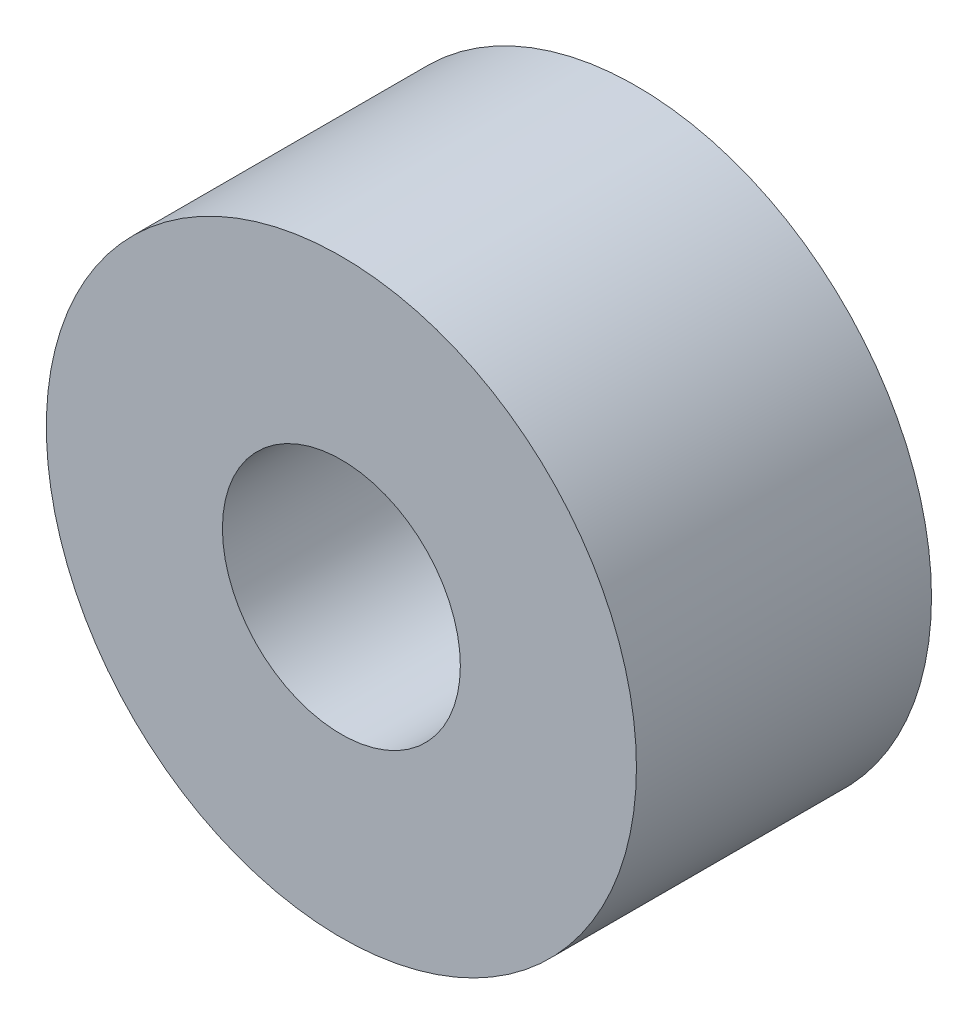
SolidWorks part; units mm, degrees
ref_plane "Front Plane" through (0, 0, 0) normal (0, 0, 1) x (1, 0, 0)
ref_plane "Top Plane" through (0, 0, 0) normal (0, 1, 0) x (1, 0, 0)
ref_plane "Right Plane" through (0, 0, 0) normal (1, 0, 0) x (0, 0, -1)
sketch "Sketch1" plane through (0, 0, 0) normal (1, 0, 0) x (0, 0, -1)
  line L0 (-3.9688, -3.2004) -> (-3.9688, 3.2004) construction
  line L1 (3.9688, -7.9375) -> (-3.9688, -7.9375) construction
  line L2 (3.9688, -7.9375) -> (3.9688, 7.9375) construction
  line L3 (3.9688, 7.9375) -> (-3.9688, 7.9375) construction
  line L4 (-3.9688, -7.9375) -> (-3.9688, 7.9375) construction
  line L5 (0, 7.9375) -> (0, -7.9375) construction
  line L6 (3.9688, 0) -> (-3.9688, 0) construction
  point P0 (0, 0)
  point P7 (-3.9688, 0)
  dimension "D1" = 6.4008
  dimension "D2" = 15.875
sketch "Sketch3" plane through (0, 0, 0) normal (0, 0, 1) x (1, 0, 0)
  circle A0 centre (0, 0) radius 3.2004 construction
  circle A1 centre (0, 0) radius 7.9375 construction
  point P6 (0, -3.2004)
  dimension "OD" = 15.875
  dimension "ID" = 6.4008
sketch "Sketch2" plane through (0, 0, 0) normal (0, 0, 1) x (1, 0, 0)
  circle A0 centre (0, 0) radius 7.9375
  circle A1 centre (0, 0) radius 3.2004
extrude "Extrude1" add sketch "Sketch2" along normal up to vertex and the other way up to vertex up to point (0, -7.9375, 3.9688) other way up to point (0, 7.9375, -3.9688)
equation "\"D1@Sketch1\"=\"ID@Sketch3\""
equation "\"D2@Sketch1\"=\"OD@Sketch3\""
